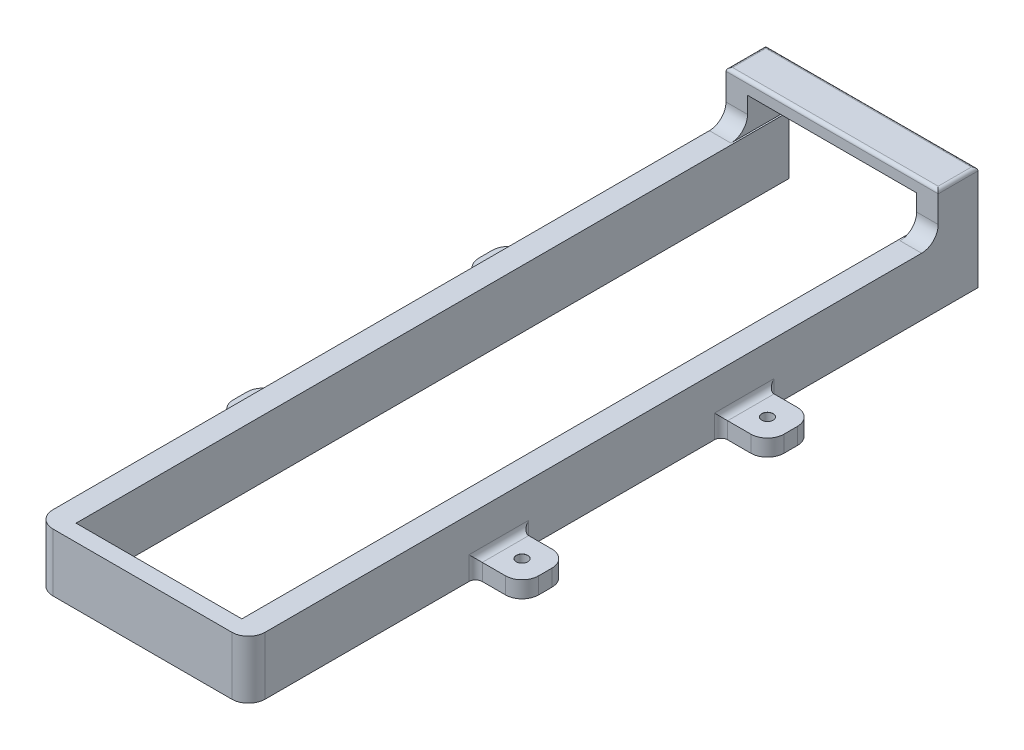
SolidWorks part; units mm, degrees
ref_plane "Front Plane" through (0, 0, 0) normal (0, 0, 1) x (1, 0, 0)
ref_plane "Top Plane" through (0, 0, 0) normal (0, 1, 0) x (1, 0, 0)
ref_plane "Right Plane" through (0, 0, 0) normal (1, 0, 0) x (0, 0, -1)
sketch "Sketch1" plane through (0, 0, 0) normal (0, 1, 0) x (1, 0, 0)
  line L0 (25, 107.5) -> (35, 107.5)
  line L2 (-25, 107.5) -> (-25, -107.5)
  line L3 (-25, -107.5) -> (25, -107.5)
  line L4 (25, 107.5) -> (25, -107.5)
  line L5 (-25, 107.5) -> (25, -107.5) construction
  line L6 (-25, -107.5) -> (25, 107.5) construction
  line L7 (35, 107.5) -> (35, -117.5)
  line L8 (35, -117.5) -> (-35, -117.5)
  line L9 (-35, -117.5) -> (-35, 107.5)
  line L10 (-35, 107.5) -> (-25, 107.5)
  point P0 (0, 0)
  dimension "D1" = 50
  dimension "D2" = 215
  dimension "D3" = 50
  dimension "D4" = 10
  dimension "D5" = 10
  dimension "D6" = 10
extrude "Boss-Extrude1" add sketch "Sketch1" along normal mid plane 17.5
sketch "Sketch2" plane through (0, 0, -107.5) normal (0, 0, -1) x (-1, 0, 0)
  line L1 (-35, 8.75) -> (-25, 8.75)
  line L2 (-35, 8.75) -> (-35, 18.75)
  line L3 (-35, 18.75) -> (-25, 18.75)
  line L4 (-25, 8.75) -> (-25, 18.75)
  line L5 (25, 8.75) -> (35, 8.75)
  line L6 (25, 8.75) -> (25, 18.75)
  line L7 (25, 18.75) -> (35, 18.75)
  line L8 (35, 8.75) -> (35, 18.75)
  line L9 (-35, 18.75) -> (35, 18.75)
  line L10 (-35, 18.75) -> (-35, 22.75)
  line L11 (-35, 22.75) -> (35, 22.75)
  line L12 (35, 18.75) -> (35, 22.75)
  line M7 (-25, 8.75) -> (-35, 8.75)
  dimension "D1" = 10
  dimension "D2" = 4
  dimension "D3" = 70
  dimension "D4" = 10
extrude "Boss-Extrude2" add sketch "Sketch2" against normal blind 12 contours L4 L3 L2 M7 | L7 L12 L11 L10 L3 L9 | L5 L8 L7 L6 region at (30, 13.75, -107.5) region at (0, 20.75, -107.5) region at (-30, 13.75, -107.5)
sketch "Sketch3" plane through (0, 8.75, 0) normal (0, 1, 0) x (1, 0, 0)
  line L0 (35, -117.5) -> (35, 95.5) construction
  line L1 (-35, -117.5) -> (35, -117.5)
  line L2 (-35, -117.5) -> (-35, -112.5)
  line L3 (-32, -112.5) -> (32, -112.5)
  line L4 (35, -117.5) -> (35, -112.5)
  line L6 (-35, 107.5) -> (-32, 107.5)
  line L7 (-35, 107.5) -> (-35, -112.5)
  line L9 (-32, 107.5) -> (-32, -112.5)
  line L10 (35, 107.5) -> (32, 107.5)
  line L11 (35, 107.5) -> (35, -112.5)
  line L13 (32, 107.5) -> (32, -112.5)
  dimension "D1" = 5
  dimension "D2" = 3
  dimension "D3" = 3
extrude "Cut-Extrude1" cut sketch "Sketch3" against normal through all both and the other way through all
sketch "Sketch4" plane through (0, 8.75, 0) normal (0, 1, 0) x (1, 0, 0)
  line L0 (-32, -112.5) -> (-32, 95.5) construction
  line L1 (-32, 44) -> (-46, 44)
  line L2 (-32, 44) -> (-32, 30)
  line L3 (-32, 30) -> (-46, 30)
  line L4 (-46, 44) -> (-46, 30)
  line L10 (0, 0) -> (0, 40.3812) construction
  line L11 (46, -30) -> (46, -44)
  line L12 (-32, -30) -> (-46, -30)
  line L13 (-32, -30) -> (-32, -44)
  line L14 (-32, -44) -> (-46, -44)
  line L15 (-46, -30) -> (-46, -44)
  line L16 (32, -44) -> (46, -44)
  line L17 (32, -30) -> (32, -44)
  line L18 (32, -30) -> (46, -30)
  line L19 (46, 44) -> (46, 30)
  line L20 (32, 30) -> (46, 30)
  line L21 (32, 44) -> (32, 30)
  line L22 (32, 44) -> (46, 44)
  dimension "D1" = 14
  dimension "D2" = 14
  dimension "D3" = 14
  dimension "D4" = 14
  dimension "D5" = 30
  dimension "D6" = 30
extrude "Boss-Extrude3" add sketch "Sketch4" against normal up to surface (17.5 mm away) up to face at (0, -8.75, 1.25)
sketch "Sketch7" plane through (0, 8.75, 0) normal (0, 1, 0) x (1, 0, 0)
  line L1 (-46, 44) -> (-32, 44)
  line L2 (-46, 44) -> (-46, 30)
  line L3 (-46, 30) -> (-32, 30)
  line L4 (-32, 44) -> (-32, 30)
  line L5 (32, 44) -> (46, 44)
  line L6 (32, 44) -> (32, 30)
  line L7 (32, 30) -> (46, 30)
  line L8 (46, 44) -> (46, 30)
  line L9 (32, -30) -> (46, -30)
  line L10 (32, -30) -> (32, -44)
  line L11 (32, -44) -> (46, -44)
  line L12 (46, -30) -> (46, -44)
  line L13 (-46, -30) -> (-32, -30)
  line L14 (-46, -30) -> (-46, -44)
  line L15 (-46, -44) -> (-32, -44)
  line L16 (-32, -30) -> (-32, -44)
extrude "Cut-Extrude2" cut sketch "Sketch7" against normal blind 12.5
sketch "Sketch11" plane through (0, 0, -107.5) normal (0, 0, -1) x (-1, 0, 0)
  line L1 (-25.5, 8.75) -> (25.5, 8.75)
  line L2 (-25.5, 8.75) -> (-25.5, 18.75)
  line L3 (-25.5, 18.75) -> (25.5, 18.75)
  line L4 (25.5, 8.75) -> (25.5, 18.75)
  dimension "D1" = 10
  dimension "D2" = 0.5
  dimension "D3" = 0.5
  dimension "D4" = 51
extrude "Cut-Extrude3" cut sketch "Sketch11" against normal through all
hole_wizard "M3 Clearance Hole1" positions "Sketch8" profile "Sketch9" hole size "M3" standard "ANSI Metric" end condition through all
sketch "Sketch8" plane through (0, -3.75, 0) normal (0, 1, 0) x (1, 0, 0)
  line L0 (-46, 44) -> (-46, 30) construction
  line L1 (-46, 30) -> (-32, 30) construction
  point P0 (-39, 37)
  point P2 (39, 37)
  point P4 (39, -37)
  point P6 (-39, -37)
  dimension "D1" = 7
  dimension "D2" = 85
  dimension "D3" = 7
  dimension "D4" = 67
sketch "Sketch9" plane through (-39, -3.75, -37) normal (1, 0, 0) x (0, 0, 1)
  line L0 (0, 0) -> (0, 5)
  line L1 (0, 5) -> (1.7, 5)
  line L2 (1.7, 5) -> (1.7, 0.025)
  line L3 (1.7, 0.025) -> (1.725, 0)
  line L5 (1.725, 0) -> (0, 0)
  line L6 (-1.7, 0.025) -> (-1.725, 0) construction
  line L11 (0, -6.35) -> (0, 107.95) construction
  dimension "Thru Hole Dia." = 3.4
  dimension "Thru Hole Depth" = 5
  dimension "Near C'Sink Dia." = 3.45
  dimension "Near C'Sink Angle" = 90
fillet "Fillet1" radius 2 12 edges at (-32, -6.25, -44) (-32, -3.75, -37) (-32, -6.25, -30) (-32, -6.25, 30) (-32, -3.75, 37) (-32, -6.25, 44) (32, -6.25, 44) (32, -3.75, 37) (32, -6.25, 30) (32, -6.25, -44) (32, -6.25, -30) (32, -3.75, -37)
fillet "Fillet2" radius 5 12 edges at (-46, -6.25, -30) (-46, -6.25, -44) (-46, -6.25, 30) (-46, -6.25, 44) (46, -6.25, -44) (46, -6.25, -30) (46, -6.25, 30) (46, -6.25, 44) (-32, 0, 112.5) (32, 0, 112.5) (-28.75, 8.75, -95.5) (28.75, 8.75, -95.5)
fillet "Fillet4" radius 1 4 edges at (32, 22.75, -101.5) (0, 22.75, -95.5) (-32, 22.75, -101.5) (0, 22.75, -107.5)
